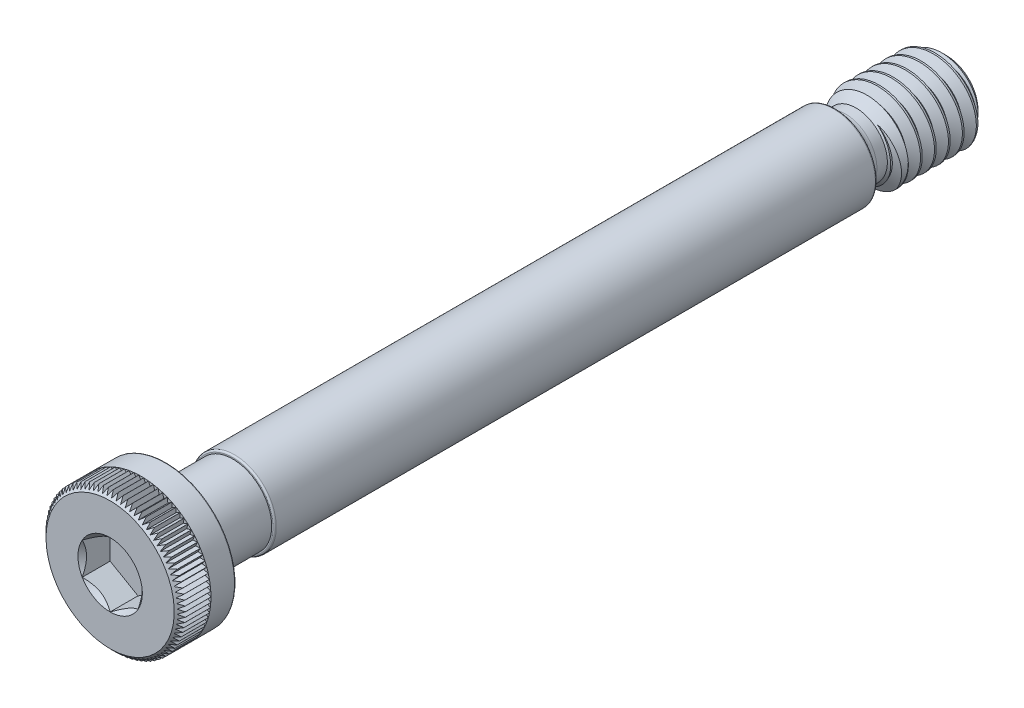
SolidWorks part; units mm, degrees
other "DetailItem1"
other "DetailItem2"
other "DetailItem5"
other "DetailItem6"
ref_plane "Front" through (0, 0, 0) normal (0, 0, 1) x (1, 0, 0)
ref_plane "Top" through (0, 0, 0) normal (0, 1, 0) x (1, 0, 0)
ref_plane "Right" through (0, 0, 0) normal (1, 0, 0) x (0, 0, -1)
sketch "Sketch1" plane through (0, 0, 0) normal (1, 0, 0) x (0, 0, -1)
  line L7 (-15, 0) -> (15, 0) construction
  line L8 (15, 1.125) -> (14.625, 1.5)
  line L9 (14.9687, 1.5541) -> (15.2188, 1.1211) construction
  line L16 (15.2188, 1.1211) -> (15.4687, 1.5541) construction
  line L22 (15, 1.5) -> (15, 0)
  line L23 (-13, 2.5) -> (-13, 1.395)
  line L24 (-13, 1.395) -> (-10.6, 1.395)
  line L25 (15.4687, 1.5541) -> (14.9687, 1.5541) construction
  line L26 (11.375, 1.125) -> (11.75, 1.125)
  line L27 (11.75, 1.125) -> (12.125, 1.5)
  line L29 (-15, 2.5) -> (-15, 0)
  line L30 (-15, 2.5) -> (-13, 2.5)
  line L33 (-10.6, 1.5) -> (-10.6, 1.395)
  line L34 (-10.6, 1.5) -> (11, 1.5)
  line L35 (15, 1.5) -> (12.125, 1.5)
  line L37 (14.9844, 1.5271) -> (15.4531, 1.5271)
  line L38 (15.4531, 1.5271) -> (15.25, 1.1752)
  line L39 (15.25, 1.1752) -> (15.1875, 1.1752)
  line L40 (15.1875, 1.1752) -> (14.9844, 1.5271)
  line L41 (15.2187, 1.1752) -> (15.2188, 1.1211) construction
  line L42 (15, 1.5) -> (15.4375, 1.5) construction
  line L47 (15.2187, 1.5541) -> (15.2187, 1.5) construction
  line L48 (11, 1.5) -> (11.375, 1.5) construction
  line L49 (-14.8, 2.5) -> (-15, 2.3)
  line L50 (15, -1.5) -> (12.125, -1.5)
  line L51 (-14.76, 2.5) -> (-14.76, 2.3) construction
  line L52 (-14.76, 2.3) -> (-13.04, 2.3) construction
  line L53 (-13.9, 2.3) -> (-13.9, 2.5) construction
  arc A0 (11, 1.5) -> (11.375, 1.125) centre (11.375, 1.5) ccw
  arc A1 (10.9442, 1.5) -> (11.0036, 1.4483) centre (10.9442, 1.44) cw
  arc A2 (-10.6, 1.44) -> (-10.54, 1.5) centre (-10.54, 1.44) cw
  arc A4 (-13.04, 2.5) -> (-13, 2.46) centre (-13.04, 2.46) cw
  point P2 (0, 0)
  point P20 (15.2187, 1.5271)
  point P44 (-13.9, 2.5)
  point P45 (15, 1.5)
  point P46 (-14.76, 2.5)
  point P47 (-13, 1.9475)
  point P48 (11.75, 1.9475)
  point P51 (-14, 0)
  point P52 (14, 1.5)
  point P54 (15, 1.9475)
  point P57 (15, -1.9475)
  point P58 (11.75, -1.9475)
  point P59 (11, -1.5)
  dimension "D6" = 0.06
  dimension "D8" = 0.04
  dimension "D1" = 45
  dimension "Pitch" = 0.5
  dimension "D3" = 0.0625
  dimension "D2" = 0.375
  dimension "D4" = 2.79
  dimension "D5" = 2.4
  dimension "D9" = 0.2
  dimension "D12" = 0.04
  dimension "D10" = 1
  dimension "D11" = 1
  dimension "Shoulder Diameter" = 3
  dimension "Thread Length" = 4
sketch "Sketch2" plane through (0, 0, 0) normal (0, 0, 1) x (1, 0, 0)
  line L9 (0, 1.1547) -> (-1, 0.5774)
  line L11 (-0.0873, 2.5) -> (0.0873, 2.5)
  line L12 (0.0873, 2.5) -> (0, 2.3488)
  line L13 (0, 2.3488) -> (-0.0873, 2.5)
  line L14 (0, 0) -> (-0.0873, 2.5) construction
  line L15 (0, 0) -> (0.0873, 2.5) construction
  line L16 (-1, 0.5774) -> (-1, -0.5774)
  line L17 (-1, -0.5774) -> (0, -1.1547)
  line L18 (0, -1.1547) -> (1, -0.5774)
  line L19 (1, -0.5774) -> (1, 0.5774)
  line L20 (1, 0.5774) -> (0, 1.1547)
  circle A0 centre (0, 0) radius 1 construction
  circle A2 centre (0, 0) radius 2.5
sketch "Sketch12" plane through (0, 0, 0) normal (1, 0, 0) x (0, 0, -1)
  line L0 (-15, 0) -> (-15, 2.3)
  line L1 (-15, 2.3) -> (-14.8, 2.5)
  line L2 (-14.8, 2.5) -> (-13.04, 2.5)
  line L3 (15, 1.125) -> (14.625, 1.5) construction
  line L5 (11.75, 1.125) -> (12.125, 1.5) construction
  line L7 (11.375, 1.125) -> (11.75, 1.125) construction
  line L8 (15, 1.125) -> (14.625, 1.5)
  line L9 (11.75, 1.125) -> (12.125, 1.5)
  line L11 (11.375, 1.125) -> (11.75, 1.125)
  line L12 (-13, 1.395) -> (-13, 2.46)
  line L13 (-13, 1.395) -> (-10.6, 1.395)
  line L14 (-10.6, 1.395) -> (-10.6, 1.44)
  line L15 (-10.54, 1.5) -> (10.9442, 1.5)
  line L16 (12.125, 1.5) -> (14.625, 1.5)
  line L17 (15, 1.125) -> (15, 0)
  line L18 (15, 0) -> (-15, 0)
  arc A0 (-13, 2.46) -> (-13.04, 2.5) centre (-13.04, 2.46) ccw construction
  arc A1 (-13, 2.46) -> (-13.04, 2.5) centre (-13.04, 2.46) ccw
  arc A5 (11, 1.5) -> (11.375, 1.125) centre (11.375, 1.5) ccw construction
  arc A6 (11.0036, 1.4483) -> (10.9442, 1.5) centre (10.9442, 1.44) ccw construction
  arc A7 (-10.54, 1.5) -> (-10.6, 1.44) centre (-10.54, 1.44) ccw construction
  arc A8 (11.0036, 1.4483) -> (11.375, 1.125) centre (11.375, 1.5) ccw
  arc A9 (11.0036, 1.4483) -> (10.9442, 1.5) centre (10.9442, 1.44) ccw
  arc A10 (-10.54, 1.5) -> (-10.6, 1.44) centre (-10.54, 1.44) ccw
revolve "Revolve1" add sketch "Sketch12" angle 360 mid plane about L18
sketch "Sketch8" plane through (0, 0, 15) normal (0, 0, 1) x (1, 0, 0)
  line L6 (0, -1.1547) -> (1, -0.5774) construction
  line L7 (-1, -0.5774) -> (0, -1.1547) construction
  line L8 (-1, 0.5774) -> (-1, -0.5774) construction
  line L9 (0, 1.1547) -> (-1, 0.5774) construction
  line L10 (1, 0.5774) -> (0, 1.1547) construction
  line L11 (1, -0.5774) -> (1, 0.5774) construction
  line L12 (0, -1.1547) -> (1, -0.5774)
  line L13 (-1, -0.5774) -> (0, -1.1547)
  line L14 (-1, 0.5774) -> (-1, -0.5774)
  line L15 (0, 1.1547) -> (-1, 0.5774)
  line L16 (1, 0.5774) -> (0, 1.1547)
  line L17 (1, -0.5774) -> (1, 0.5774)
extrude "Cut-Extrude2" cut sketch "Sketch8" against normal up to vertex (1 mm away) up to point (0, 0, 14)
sketch "Sketch9" plane through (0, 0, 15) normal (0, 0, 1) x (1, 0, 0)
  circle A1 centre (0, 0) radius 1.1547
extrude "Cut-Extrude4" cut sketch "Sketch9" against normal up to vertex (1 mm away) draft 45 up to point (0, 0, 14)
ref_axis "Center Axis1" through (0, 0, -10.7727) along (0, 0, 1)
ref_plane "Contact Plane1" through (0, 0, -15) normal (0, 0, 1) x (1, 0, 0)
ref_plane "Contact Plane2" through (0, 0, 13) normal (0, 0, 1) x (1, 0, 0)
ref_plane "Plane2" through (0, 0, -11.75) normal (0, 0, -1) x (-1, 0, 0)
split "Split1" trim tools "Plane2" bodies to split 118 resulting bodies 122 123
sketch "Sketch3" plane through (0, 0, -15) normal (0, 0, 1) x (1, 0, 0)
  circle A0 centre (0, 0) radius 1.5 construction
  circle A2 centre (0, 0) radius 1.5
curve "Helix/Spiral1" pitch 0.5 height 4 radius 1.5 centre (0, 0, -15) axis (0, 0, 1) start towards (0, 1, 0)
sketch "Sketch13" plane through (0, 0, 0) normal (1, 0, 0) x (0, 0, -1)
  line L0 (14.9844, 1.5271) -> (15.4531, 1.5271) construction
  line L1 (15.1875, 1.1752) -> (14.9844, 1.5271) construction
  line L2 (15.25, 1.1752) -> (15.1875, 1.1752) construction
  line L3 (15.4531, 1.5271) -> (15.25, 1.1752) construction
  line L16 (14.9844, 1.5271) -> (15.4531, 1.5271)
  line L17 (15.1875, 1.1752) -> (14.9844, 1.5271)
  line L18 (15.25, 1.1752) -> (15.1875, 1.1752)
  line L19 (15.4531, 1.5271) -> (15.25, 1.1752)
sweep "Cut-Sweep1" cut profiles "Sketch13" path "Helix/Spiral1" align with end faces yes
combine bodies "Combine1" operation type add bodies to combine 123 126
ref_plane "Plane1" through (0, 0, 14.76) normal (0, 0, 1) x (1, 0, 0)
sketch "Sketch11" plane through (0, 0, 14.76) normal (0, 0, 1) x (1, 0, 0)
  line L0 (0.0873, 2.5) -> (0, 2.3488) construction
  line L1 (0, 2.3488) -> (-0.0873, 2.5) construction
  line L2 (-0.0873, 2.5) -> (0.0873, 2.5) construction
  line L3 (0.0873, 2.5) -> (0, 2.3488)
  line L4 (0, 2.3488) -> (-0.0873, 2.5)
  line L5 (-0.0873, 2.5) -> (0.0873, 2.5)
  point P3 (0, 0.0018)
  point P8 (2.3908, 0.7309)
extrude "Cut-Extrude5" cut sketch "Sketch11" against normal blind 0.875 and the other way through all
pattern_circular "CirPattern1" count 90 over 360 about axis through (0, 0, 14.8) along (0, 0, -1) of "Cut-Extrude5"
equation "\"D3@Sketch1\"=\"Pitch@Sketch1\"/8"
equation "\"D2@Sketch1\"=\"Pitch@Sketch1\"*.75"
equation "\"D4@Sketch1\"=\"Shoulder Diameter@Sketch1\"*.93"
equation "\"D5@Sketch1\"=\"Shoulder Length@Sketch1\"*.1"
equation "\"D6@Sketch1\"=\"Shoulder Diameter@Sketch1\"*.04*0.5"
equation "\"D8@Sketch1\"=\"Head Height@Sketch1\"*.02"
equation "\"D9@Sketch1\"=\"Head Height@Sketch1\"*.1"
equation "\"D4@Helix/Spiral1\"=\"Pitch@Sketch1\""
equation "\"D3@Helix/Spiral1\"=\"Thread Length@Sketch1\""
equation "\"D1@CirPattern1\" = 360 / \"Knurl Angle@Sketch2\""
equation "\"D12@Sketch1\"=\"Head Height@Sketch1\"*.02"
equation "\"D10@Sketch1\"=\"Pitch@Sketch1\"*2"
equation "\"D11@Sketch1\"=\"Head Height@Sketch1\"*0.5"
equation "\"D1@Cut-Extrude5\"=\"Head Height@Sketch1\"*.4375"
